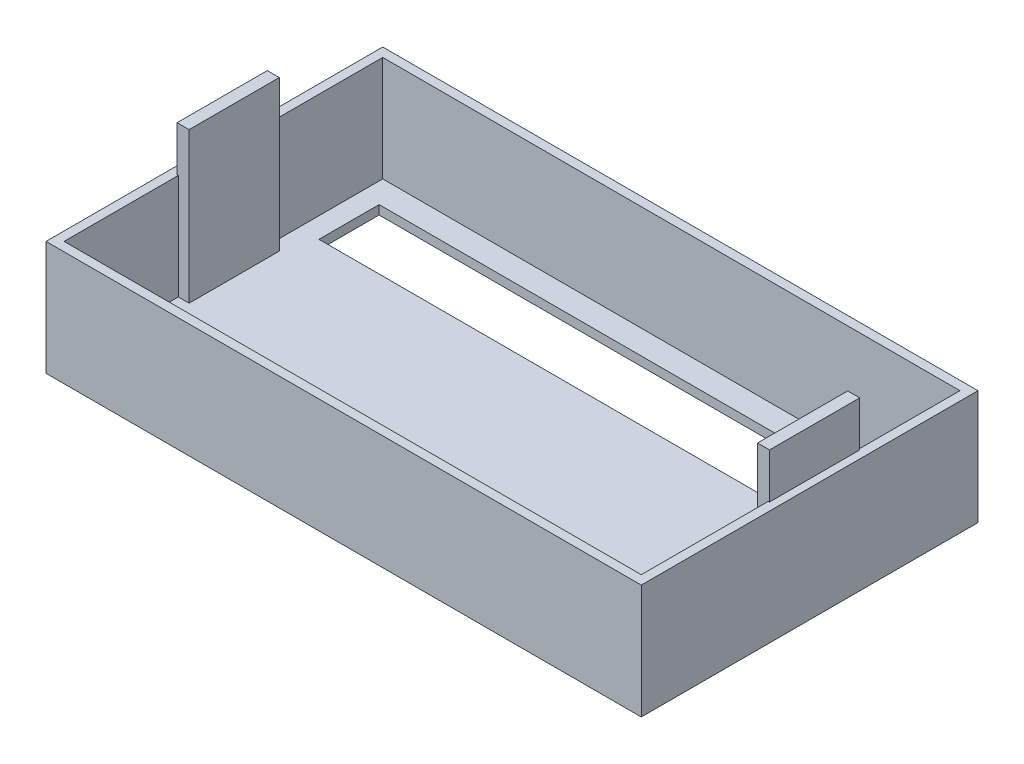
SolidWorks part; units mm, degrees
ref_plane "Front Plane" through (0, 0, 0) normal (0, 0, 1) x (1, 0, 0)
ref_plane "Top Plane" through (0, 0, 0) normal (0, 1, 0) x (1, 0, 0)
ref_plane "Right Plane" through (0, 0, 0) normal (1, 0, 0) x (0, 0, -1)
sketch "Sketch1" plane through (0, 0, 0) normal (0, 1, 0) x (1, 0, 0)
  line L1 (49.5, 28) -> (-49.5, 28)
  line L2 (49.5, 28) -> (49.5, -28)
  line L3 (49.5, -28) -> (-49.5, -28)
  line L4 (-49.5, 28) -> (-49.5, -28)
  line L5 (49.5, 28) -> (-49.5, -28) construction
  line L6 (49.5, -28) -> (-49.5, 28) construction
  point P0 (0, 0)
  dimension "D1" = 99
  dimension "D2" = 56
extrude "Boss-Extrude1" add sketch "Sketch1" along normal blind 19
shell "Shell1" thickness 1.5 removed face at (0, 19, 0)
sketch "Sketch10" plane through (0, 1.5, 0) normal (0, 1, 0) x (1, 0, 0)
  line L0 (-48, 26.5) -> (-48, -26.5) construction
  line L1 (-48.2, 7.5) -> (-46.2, 7.5)
  line L2 (-48.2, 7.5) -> (-48.2, -7.5)
  line L3 (-48.2, -7.5) -> (-46.2, -7.5)
  line L4 (-46.2, 7.5) -> (-46.2, -7.5)
  line L5 (48, 26.5) -> (-48, 26.5) construction
  dimension "D1" = 2
  dimension "D2" = 0.2
  dimension "D3" = 15
  dimension "D4" = 19
extrude "Boss-Extrude4" add sketch "Sketch10" along normal blind 25
sketch "Sketch12" plane through (0, 1.5, 0) normal (0, 1, 0) x (1, 0, 0)
  line L0 (48, -26.5) -> (48, 26.5) construction
  line L1 (48.2, 9.6307) -> (46.2, 9.6307)
  line L2 (48.2, 9.6307) -> (48.2, -5.3693)
  line L3 (48.2, -5.3693) -> (46.2, -5.3693)
  line L4 (46.2, 9.6307) -> (46.2, -5.3693)
  dimension "D1" = 2
  dimension "D2" = 0.2
  dimension "D3" = 15
extrude "Boss-Extrude5" add sketch "Sketch12" along normal blind 25
sketch "Sketch14" plane through (0, 1.5, 0) normal (0, 1, 0) x (1, 0, 0)
  line L0 (48, 26.5) -> (-48, 26.5) construction
  line L1 (-44.6, 22.5) -> (44.6, 22.5)
  line L2 (-44.6, 22.5) -> (-44.6, 12.5)
  line L3 (-44.6, 12.5) -> (44.6, 12.5)
  line L4 (44.6, 22.5) -> (44.6, 12.5)
  line L6 (48, 9.6307) -> (48, 26.5) construction
  line L7 (-48, 26.5) -> (-48, 7.5) construction
  dimension "D1" = 10
  dimension "D2" = 4
  dimension "D3" = 3.4
  dimension "D4" = 3.4
extrude "Cut-Extrude3" cut sketch "Sketch14" against normal blind 10
